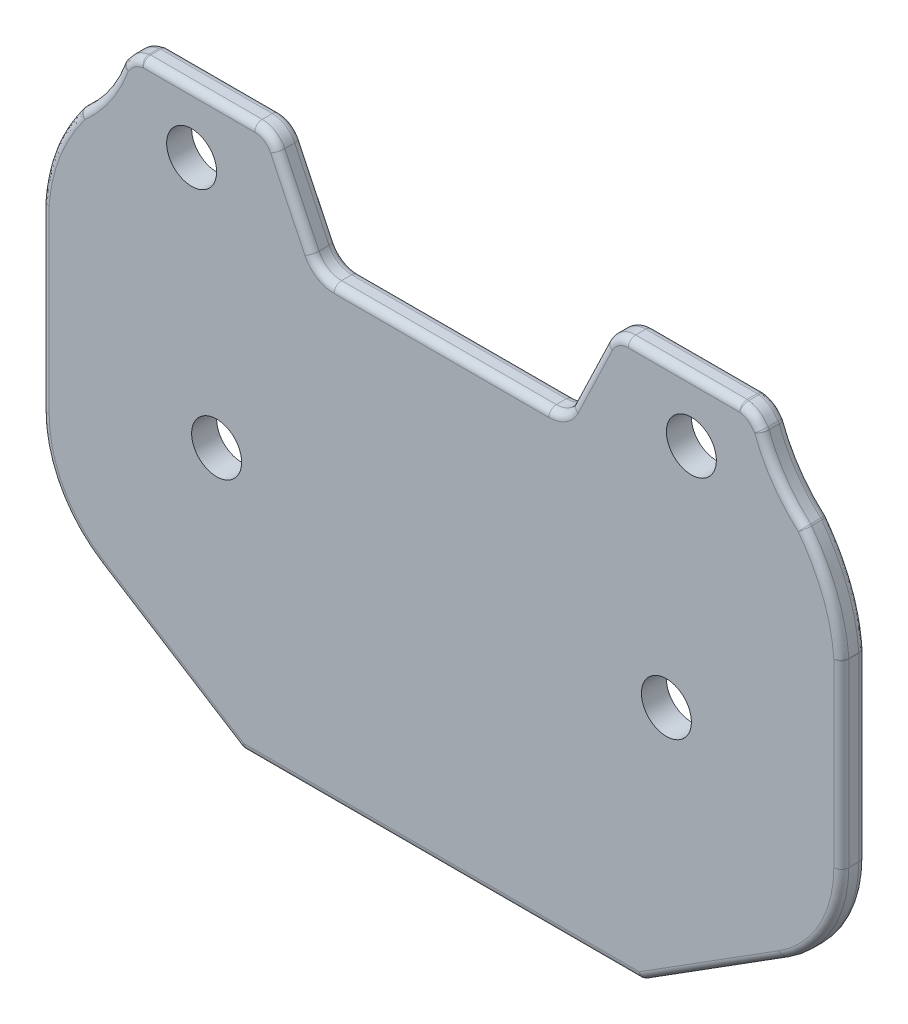
SolidWorks part; units mm, degrees
ref_plane "Front Plane" through (0, 0, 0) normal (0, 0, 1) x (1, 0, 0)
ref_plane "Top Plane" through (0, 0, 0) normal (0, 1, 0) x (1, 0, 0)
ref_plane "Right Plane" through (0, 0, 0) normal (1, 0, 0) x (0, 0, -1)
sketch "Sketch1" plane through (0, 0, 0) normal (0, 0, 1) x (1, 0, 0)
  line L0 (0, 0) -> (0, -18) construction
  line L1 (-4.2974, 0) -> (4.2974, 0)
  line L2 (5.1991, 0.5675) -> (6.5732, 3.4325)
  line L3 (7.4749, 4) -> (13.9954, 4)
  line L5 (16, -0.9241) -> (16, -10.1965)
  line L7 (8, -18) -> (-8, -18)
  line L8 (-16, -0.9241) -> (-16, -10.1965)
  line L9 (-7.4749, 4) -> (-13.9954, 4)
  line L10 (-5.1991, 0.5675) -> (-6.5732, 3.4325)
  line L11 (8, -18) -> (13.6673, -14.4256)
  line L12 (-8, -18) -> (-13.6673, -14.4256)
  arc A0 (14.9767, 3.1923) -> (15.6436, 0.9297) centre (27.4148, 5.6289) ccw
  arc A1 (4.2974, 0) -> (5.1991, 0.5675) centre (4.2974, 1) ccw
  arc A2 (13.9954, 4) -> (14.9767, 3.1923) centre (13.9954, 3) cw
  arc A3 (6.5732, 3.4325) -> (7.4749, 4) centre (7.4749, 3) cw
  circle A4 centre (9, -8) radius 1
  arc A5 (15.6436, 0.9297) -> (16, -0.9241) centre (11, -0.9241) cw
  circle A7 centre (10, 1.5633) radius 1
  circle A9 centre (-10, 1.5633) radius 1
  arc A11 (-15.6436, 0.9297) -> (-16, -0.9241) centre (-11, -0.9241) ccw
  circle A12 centre (-9, -8) radius 1
  arc A13 (-6.5732, 3.4325) -> (-7.4749, 4) centre (-7.4749, 3) ccw
  arc A14 (-13.9954, 4) -> (-14.9767, 3.1923) centre (-13.9954, 3) ccw
  arc A15 (-4.2974, 0) -> (-5.1991, 0.5675) centre (-4.2974, 1) cw
  arc A16 (-14.9767, 3.1923) -> (-15.6436, 0.9297) centre (-27.4148, 5.6289) cw
  arc A17 (16, -10.1965) -> (13.6673, -14.4256) centre (11, -10.1965) cw
  arc A18 (-16, -10.1965) -> (-13.6673, -14.4256) centre (-11, -10.1965) ccw
  point P14 (14.8454, 4)
  point P17 (6.8454, 4)
  point P23 (16, 0.1203)
  point P26 (16, -17.8797)
  point P30 (16, -12.9543)
  point P49 (-16, -17.8797)
  point P50 (-16, 0.1203)
  point P51 (-6.8454, 4)
  point P52 (-14.8454, 4)
  point P54 (-16, -12.9543)
  dimension "D7" = 1
  dimension "D9" = 2
  dimension "D10" = 5
  dimension "D12" = 2
  dimension "D13" = 5
  dimension "D1" = 16
  dimension "D2" = 22
  dimension "D3" = 8
  dimension "D4" = 18
  dimension "D5" = 4
  dimension "D6" = 8
  dimension "D8" = 9
  dimension "D11" = 8
  dimension "D14" = 10
extrude "Boss-Extrude1" add sketch "Sketch1" along normal blind 1
sketch "Sketch2" plane through (0, 0, 1) normal (0, 0, 1) x (1, 0, 0)
  line L0 (13.9954, 4) -> (7.4749, 4) construction
  line L1 (15.9101, 0.0198) -> (17.2317, 7.7109)
  line L2 (17.2317, 7.7109) -> (-20.9941, 9.5921)
  line L3 (-20.9941, 9.5921) -> (-20.9941, -1.0931)
  line L4 (0, 0) -> (0, -5.9842) construction
  line L5 (4.2974, 0) -> (-4.2974, 0) construction
  line L6 (-20.9941, -1.0931) -> (-15.9101, 0.0198)
  line L7 (-12.625, 4) -> (12.625, 4)
  arc A0 (12.625, 4) -> (15.9101, 0.0198) centre (18.4323, 5.4473) ccw
  arc A1 (16, -0.9241) -> (15.6436, 0.9297) centre (11, -0.9241) ccw construction
  arc A2 (-12.625, 4) -> (-15.9101, 0.0198) centre (-18.4323, 5.4473) cw
extrude "Cut-Extrude1" cut sketch "Sketch2" against normal through all both and the other way through all
sketch "Sketch3" plane through (0, 0, 1) normal (0, 0, 1) x (1, 0, 0)
  line L0 (-16, -0.9241) -> (-16, -10.1965) construction
  line L1 (-7.4749, 4) -> (-12.625, 4) construction
  line L2 (-11.9674, 4) -> (-11.9674, 4.7765)
  line L3 (-11.9674, 4.7765) -> (-13.2885, 4.686)
  line L4 (-13.2885, 4.686) -> (-13.1238, 3.6155)
  line L5 (-13.1238, 3.6155) -> (-12.797, 3.4316)
  line L6 (-14.4975, 0.9377) -> (-16.434, 1.2066)
  line L7 (-16.434, 1.2066) -> (-17.9262, -1.9247)
  line L8 (-17.9262, -1.9247) -> (-16, -2.9567)
  line L9 (0, 0) -> (0, 6.0095) construction
  line L10 (17.9262, -1.9247) -> (16, -2.9567)
  line L11 (16.434, 1.2066) -> (17.9262, -1.9247)
  line L12 (14.4975, 0.9377) -> (16.434, 1.2066)
  line L13 (13.1238, 3.6155) -> (12.797, 3.4316)
  line L14 (13.2885, 4.686) -> (13.1238, 3.6155)
  line L15 (11.9674, 4.7765) -> (13.2885, 4.686)
  line L16 (11.9674, 4) -> (11.9674, 4.7765)
  arc A0 (-15.9101, 0.0198) -> (-12.625, 4) centre (-18.4323, 5.4473) ccw construction
  spline S0 degree 2 poles (-16, -2.9567) (-15.8545, -0.8747) (-14.4975, 0.9377) knots 0 0 0 1 1 1
  spline S1 degree 3 poles (-12.797, 3.4316) (-12.5859, 3.692) (-12.4909, 3.8896) (-11.9674, 4) knots 0 0 0 0 1 1 1 1
  spline S2 degree 3 poles (12.797, 3.4316) (12.5859, 3.692) (12.4909, 3.8896) (11.9674, 4) knots 0 0 0 0 1 1 1 1
  spline S3 degree 2 poles (16, -2.9567) (15.8545, -0.8747) (14.4975, 0.9377) knots 0 0 0 1 1 1
extrude "Cut-Extrude2" cut sketch "Sketch3" against normal through all both and the other way through all
fillet "Fillet1" radius 0.3 54 edges at (0, 0, 0) (4.8301, 0.1537, 0) (0, 0, 1) (-4.8301, 0.1537, 0) (4.8301, 0.1537, 1) (5.8861, 2, 0) (-4.8301, 0.1537, 1) (-5.8861, 2, 0) (5.8861, 2, 1) (6.9422, 3.8463, 0) (-5.8861, 2, 1) (-6.9422, 3.8463, 0) (6.9422, 3.8463, 1) (9.7211, 4, 0) (-6.9422, 3.8463, 1) (-9.7211, 4, 0) (12.797, 3.4316, 0.5) (13.4874, 2.0757, 0) (-12.797, 3.4316, 0.5) (-13.4874, 2.0757, 0) (13.4874, 2.0757, 1) (14.4975, 0.9377, 0.5) (-13.4874, 2.0757, 1) (-14.4975, 0.9377, 0.5) (16, -6.5766, 0) (-16, -6.5766, 0) (15.3782, -12.6113, 0) (-15.3782, -12.6113, 0) (15.3782, -12.6113, 1) (10.8337, -16.2128, 0) (0, -18, 0) (-10.8337, -16.2128, 0) (-15.3782, -12.6113, 1) (10.8337, -16.2128, 1) (8, -18, 0.5) (-8, -18, 0.5) (-10.8337, -16.2128, 1) (0, -18, 1)
